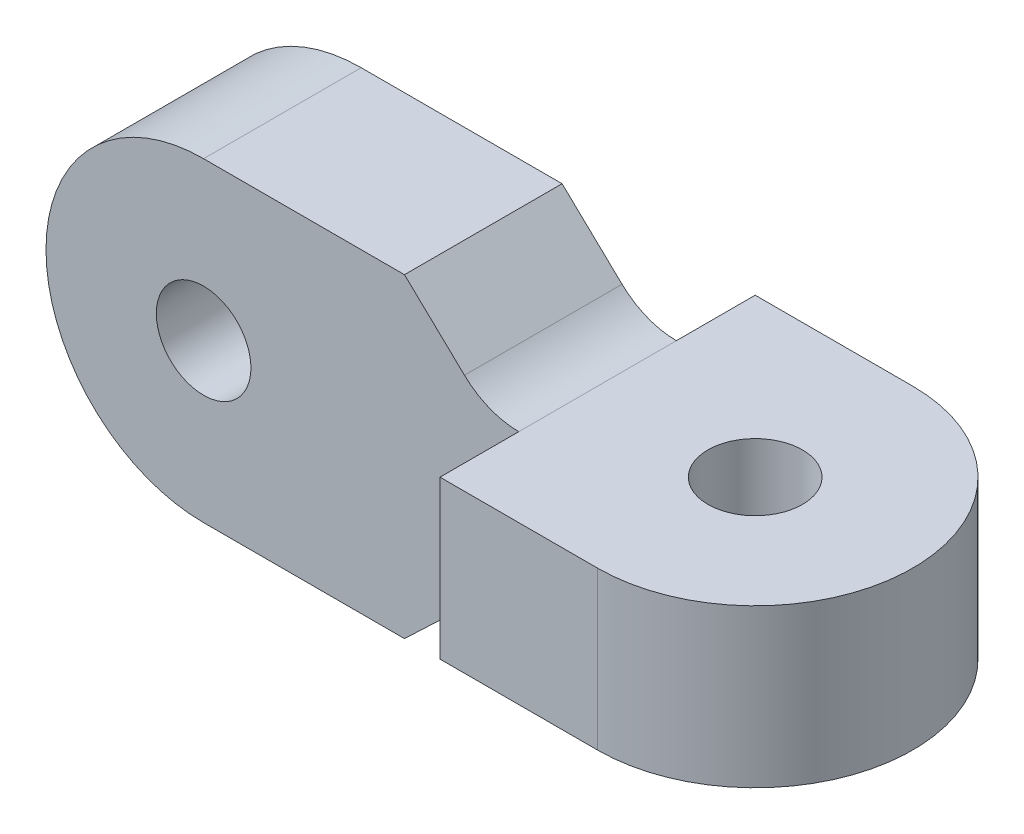
SolidWorks part; units mm, degrees
ref_plane "Alzado" through (0, 0, 0) normal (0, 0, 1) x (1, 0, 0)
ref_plane "Planta" through (0, 0, 0) normal (0, 1, 0) x (1, 0, 0)
ref_plane "Vista lateral" through (0, 0, 0) normal (1, 0, 0) x (0, 0, -1)
sketch "Croquis1" plane through (0, 0, 0) normal (0, 0, 1) x (1, 0, 0)
  line L0 (0, 5) -> (20.8673, 5) construction
  line L1 (0, 0) -> (15, 0)
  line L2 (0, 0) -> (0, 10)
  line L3 (0, 10) -> (15, 10)
  line L4 (15, 0) -> (15, 2.5)
  line L5 (15, 7.5) -> (15, 10)
  line L6 (25, 2.5) -> (15, 2.5)
  line L7 (25, 2.5) -> (25, 7.5)
  line L8 (25, 7.5) -> (15, 7.5)
  line L10 (25, 2.5) -> (15, 7.5) construction
  line L11 (25, 7.5) -> (15, 2.5) construction
  circle A0 centre (5, 5) radius 1.5
  point P9 (20, 5)
  dimension "D3" = 3
  dimension "D1" = 15
  dimension "D2" = 10
  dimension "D4" = 5
  dimension "D5" = 5
  dimension "D6" = 10
extrude "Saliente-Extruir1" add sketch "Croquis1" along normal blind 10
sketch "Croquis2" plane through (0, 7.5, 0) normal (0, 1, 0) x (1, 0, 0)
  line L0 (15, -5) -> (25, -5) construction
  line L1 (15, -10) -> (15, 0) construction
  line L2 (25, -10) -> (25, 0) construction
  line L3 (20, -10) -> (20.9227, -18.4345)
  line L4 (20.9227, -18.4345) -> (42.4813, -25.1353)
  line L5 (42.4813, -25.1353) -> (36.7972, -0.6047)
  line L6 (36.7972, -0.6047) -> (34.2267, 7.9895)
  line L7 (34.2267, 7.9895) -> (20.4613, 6.4837)
  line L8 (20.4613, 6.4837) -> (20, 0)
  arc A0 (20, -10) -> (20, 0) centre (20, -5) ccw
  circle A1 centre (20, -5) radius 1.5
  dimension "D1" = 3
extrude "Cortar-Extruir1" cut sketch "Croquis2" against normal blind 10
sketch "Croquis3" plane through (0, 10, 0) normal (0, 1, 0) x (1, 0, 0)
  line L0 (0, -10) -> (0, 0) construction
  line L1 (-15, -7.5) -> (15, -7.5)
  line L2 (-15, -2.5) -> (-15, 2.9541)
  line L3 (-15, -2.5) -> (15, -2.5)
  line L4 (15, -2.5) -> (15, 2.9541)
  line L5 (-15, -7.5) -> (15, -2.5) construction
  line L6 (-15, -2.5) -> (15, -7.5) construction
  line L8 (-15, -12.9541) -> (15, -12.9541)
  line L9 (-15, -12.9541) -> (-15, -7.5)
  line L10 (-15, 2.9541) -> (15, 2.9541)
  line L11 (15, -12.9541) -> (15, -7.5)
  line L12 (-15, -12.9541) -> (15, 2.9541) construction
  line L13 (-15, 2.9541) -> (15, -12.9541) construction
  point P0 (0, -5)
  point P7 (0, -5)
  dimension "D1" = 5
  dimension "D2" = 30
extrude "Cortar-Extruir2" cut sketch "Croquis3" against normal blind 10
ref_plane "Plano1" through (0, 0, 2.5) normal (0, 0, -1) x (-1, 0, 0)
fillet "Redondeo1" radius 5 2 edges at (0, 0, 5) (0, 10, 5)
sketch "Croquis4" plane through (0, 0, 7.5) normal (0, 0, 1) x (1, 0, 0)
  line L0 (13.2766, 8.1889) -> (11.3734, 10)
  line L1 (15, 10) -> (5, 10) construction
  line L2 (11.3734, 10) -> (13.2766, 11.8111)
  line L3 (0, 5) -> (-6.587, 5) construction
  line L4 (13.2766, 1.8111) -> (11.3734, 0)
  line L5 (11.3734, 0) -> (13.2766, -1.8111)
  arc A0 (13.2766, 8.1889) -> (13.2766, 11.8111) centre (15, 10) ccw
  arc A1 (13.2766, -1.8111) -> (13.2766, 1.8111) centre (15, 0) ccw
  arc A2 (0, 5) -> (5, 0) centre (5, 5) ccw construction
extrude "Cortar-Extruir3" cut sketch "Croquis4" against normal blind 10
